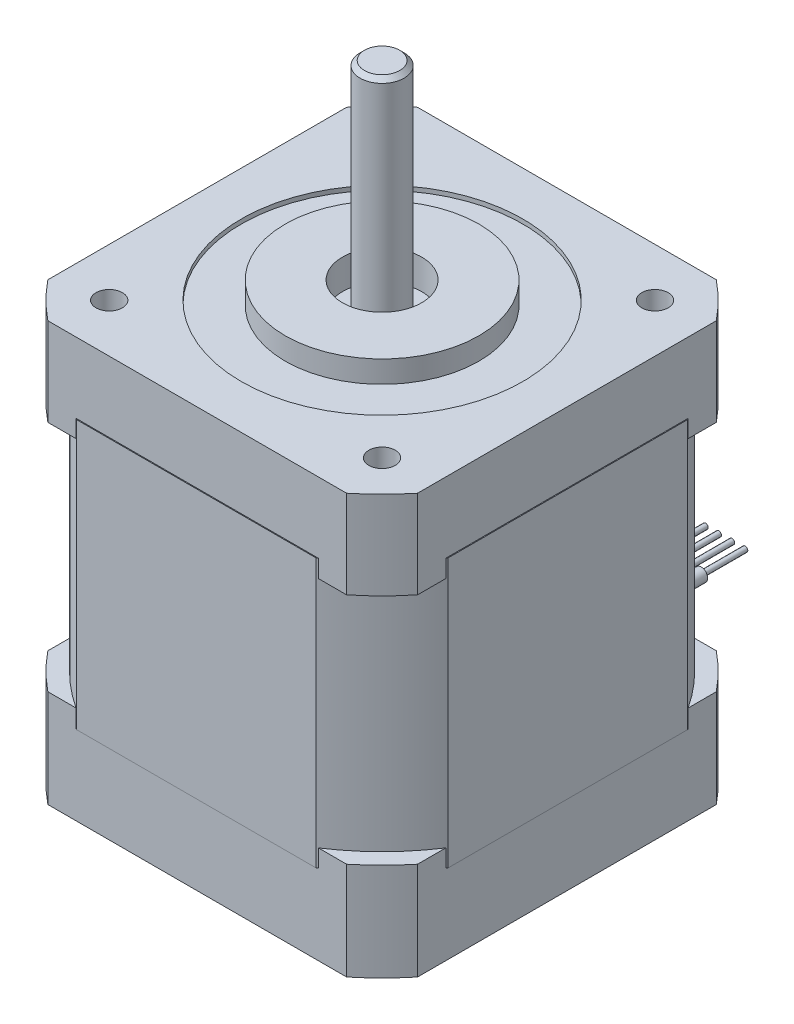
SolidWorks part; units mm, degrees
ref_plane "前视基准面" through (0, 0, 0) normal (0, 0, 1) x (1, 0, 0)
ref_plane "上视基准面" through (0, 0, 0) normal (0, 1, 0) x (1, 0, 0)
ref_plane "右视基准面" through (0, 0, 0) normal (1, 0, 0) x (0, 0, -1)
sketch "草图2" plane through (0, 0, 0) normal (0, 1, 0) x (1, 0, 0)
  line L1 (16.9706, 21) -> (-16.9706, 21)
  line L2 (21, 16.9706) -> (21, -16.9706)
  line L3 (16.9706, -21) -> (-16.9706, -21)
  line L4 (-21, 16.9706) -> (-21, -16.9706)
  arc A0 (-21, -16.9706) -> (-16.9706, -21) centre (0, 0) ccw
  arc A1 (-16.9706, 21) -> (-21, 16.9706) centre (0, 0) ccw
  arc A2 (21, 16.9706) -> (16.9706, 21) centre (0, 0) ccw
  arc A3 (16.9706, -21) -> (21, -16.9706) centre (0, 0) ccw
  circle A4 centre (-15.5, 15.5) radius 1.5
  circle A5 centre (15.5, 15.5) radius 1.5
  circle A6 centre (15.5, -15.5) radius 1.5
  circle A7 centre (-15.5, -15.5) radius 1.5
  point P0 (0, 0)
  dimension "D1" = 42
  dimension "D2" = 42
extrude "凸台-拉伸2" add sketch "草图2" along normal blind 8
sketch "草图3" plane through (0, 8, 0) normal (0, 1, 0) x (1, 0, 0)
  circle A0 centre (0, 0) radius 16
extrude "切除-拉伸1" cut sketch "草图3" against normal blind 0.5
sketch "草图4" plane through (0, 7.5, 0) normal (0, 1, 0) x (1, 0, 0)
  circle A0 centre (0, 0) radius 11
extrude "凸台-拉伸3" add sketch "草图4" along normal blind 2.5
sketch "草图5" plane through (0, 10, 0) normal (0, 1, 0) x (1, 0, 0)
  circle A0 centre (0, 0) radius 4.5
extrude "切除-拉伸2" cut sketch "草图5" against normal blind 3.4
sketch "草图6" plane through (0, 6.6, 0) normal (0, 1, 0) x (1, 0, 0)
  circle A0 centre (0, 0) radius 2.5
extrude "凸台-拉伸4" add sketch "草图6" along normal blind 25
chamfer "倒角2" distance 0.5 angle 45 1 edges at (0, 31.6, 2.5)
extrude "凸台-拉伸5" add sketch "草图2<2>" against normal blind 2
sketch "草图2<2>" plane through (0, 0, 0) normal (0, 1, 0) x (1, 0, 0) same geometry as "草图2"
sketch "草图7" plane through (0, 0, 0) normal (0, 1, 0) x (1, 0, 0)
  line L1 (13.6126, 21.1) -> (-13.6126, 21.1)
  line L2 (21.1, 13.6126) -> (21.1, -13.6126)
  line L3 (13.6126, -21.1) -> (-13.6126, -21.1)
  line L4 (-21.1, 13.6126) -> (-21.1, -13.6126)
  circle A0 centre (-15.5, 15.5) radius 1.5
  circle A1 centre (15.5, 15.5) radius 1.5
  circle A2 centre (-15.5, -15.5) radius 1.5
  circle A3 centre (15.5, -15.5) radius 1.5
  arc A4 (-21.1, -13.6126) -> (-13.6126, -21.1) centre (0, 0) ccw
  arc A5 (13.6126, -21.1) -> (21.1, -13.6126) centre (0, 0) ccw
  arc A6 (21.1, 13.6126) -> (13.6126, 21.1) centre (0, 0) ccw
  arc A7 (-13.6126, 21.1) -> (-21.1, 13.6126) centre (0, 0) ccw
  point P0 (0, 0)
extrude "凸台-拉伸6" add sketch "草图7" against normal blind 30.5
sketch "草图8" plane through (0, -30.5, 0) normal (0, -1, 0) x (1, 0, 0)
  line L0 (16.9706, 21) -> (-16.9706, 21)
  line L1 (21, 16.9706) -> (21, -16.9706)
  line L2 (16.9706, -21) -> (-16.9706, -21)
  line L3 (-21, 16.9706) -> (-21, -16.9706)
  arc A0 (-21, -16.9706) -> (-16.9706, -21) centre (0, 0) ccw
  arc A1 (-16.9706, 21) -> (-21, 16.9706) centre (0, 0) ccw
  arc A2 (21, 16.9706) -> (16.9706, 21) centre (0, 0) ccw
  arc A3 (16.9706, -21) -> (21, -16.9706) centre (0, 0) ccw
  circle A4 centre (-15.5, 15.5) radius 1.5
  circle A5 centre (15.5, 15.5) radius 1.5
  circle A6 centre (15.5, -15.5) radius 1.5
  circle A7 centre (-15.5, -15.5) radius 1.5
  point P0 (0, 0)
extrude "凸台-拉伸8" add sketch "草图8" against normal blind 2
extrude "凸台-拉伸9" add sketch "草图8<3>" along normal blind 9.1
sketch "草图8<3>" plane through (0, -30.5, 0) normal (0, -1, 0) x (1, 0, 0) same geometry as "草图8"
sketch "草图9" plane through (0, -39.6, 0) normal (0, -1, 0) x (1, 0, 0)
  circle A0 centre (0, 0) radius 3.5
  circle A1 centre (-15.5, 15.5) radius 3
  circle A2 centre (15.5, 15.5) radius 3
  circle A3 centre (-15.5, -15.5) radius 3
  circle A4 centre (15.5, -15.5) radius 3
extrude "切除-拉伸3" cut sketch "草图9" against normal blind 3.5
sketch "草图10" plane through (0, -36.1, 0) normal (0, -1, 0) x (1, 0, 0)
  circle A0 centre (15.5, -15.5) radius 2.5
  circle A1 centre (15.5, 15.5) radius 2.5
  circle A2 centre (-15.5, 15.5) radius 2.5
  circle A3 centre (-15.5, -15.5) radius 2.5
extrude "凸台-拉伸10" add sketch "草图10" along normal blind 3
extrude "凸台-拉伸11" add sketch "草图10<2>" against normal blind 39
sketch "草图10<2>" plane through (0, -36.1, 0) normal (0, -1, 0) x (1, 0, 0) same geometry as "草图10"
fillet "圆角2" radius 2 1 edges at (-15.5, -39.1, -18) type face fillet first side face at (-15.5, -39.1, -18) second side face at (-15.5, -39.1, -18)
fillet "圆角3" radius 2 1 edges at (15.5, -39.1, -18) type face fillet first side face at (15.5, -39.1, -18) second side face at (15.5, -39.1, -18)
fillet "圆角4" radius 2 1 edges at (15.5, -39.1, 13) type face fillet first side face at (15.5, -39.1, 13) second side face at (15.5, -39.1, 13)
fillet "圆角5" radius 2 1 edges at (-15.5, -39.1, 13) type face fillet first side face at (-15.5, -39.1, 13) second side face at (-15.5, -39.1, 13)
sketch "草图11" plane through (0, -39.6, 0) normal (0, -1, 0) x (1, 0, 0)
  line L1 (-15.5, 17.1) -> (-15.2, 17.1)
  line L2 (-15.2, 17.1) -> (-15.2, 15.8)
  line L3 (-15.2, 15.8) -> (-13.9, 15.8)
  line L4 (-13.9, 15.8) -> (-13.9, 15.2)
  line L5 (-13.9, 15.2) -> (-15.2, 15.2)
  line L6 (-15.2, 15.2) -> (-15.2, 13.9)
  line L7 (-15.2, 13.9) -> (-15.8, 13.9)
  line L8 (-15.8, 13.9) -> (-15.8, 15.2)
  line L9 (-15.8, 15.2) -> (-17.1, 15.2)
  line L10 (-17.1, 15.2) -> (-17.1, 15.8)
  line L11 (-17.1, 15.8) -> (-15.8, 15.8)
  line L12 (-15.8, 15.8) -> (-15.8, 17.1)
  line L13 (-15.8, 17.1) -> (-15.5, 17.1)
  line L16 (15.8, 17.1) -> (15.5, 17.1)
  line L17 (15.8, 15.8) -> (15.8, 17.1)
  line L18 (17.1, 15.8) -> (15.8, 15.8)
  line L19 (17.1, 15.2) -> (17.1, 15.8)
  line L20 (15.8, 15.2) -> (17.1, 15.2)
  line L21 (15.8, 13.9) -> (15.8, 15.2)
  line L22 (15.2, 13.9) -> (15.8, 13.9)
  line L23 (15.2, 15.2) -> (15.2, 13.9)
  line L24 (13.9, 15.2) -> (15.2, 15.2)
  line L25 (13.9, 15.8) -> (13.9, 15.2)
  line L26 (15.2, 15.8) -> (13.9, 15.8)
  line L27 (15.2, 17.1) -> (15.2, 15.8)
  line L28 (15.5, 17.1) -> (15.2, 17.1)
  line L30 (15.5, -17.1) -> (15.2, -17.1)
  line L31 (15.2, -17.1) -> (15.2, -15.8)
  line L32 (15.2, -15.8) -> (13.9, -15.8)
  line L33 (13.9, -15.8) -> (13.9, -15.2)
  line L34 (13.9, -15.2) -> (15.2, -15.2)
  line L35 (15.2, -15.2) -> (15.2, -13.9)
  line L36 (15.2, -13.9) -> (15.8, -13.9)
  line L37 (15.8, -13.9) -> (15.8, -15.2)
  line L38 (15.8, -15.2) -> (17.1, -15.2)
  line L39 (17.1, -15.2) -> (17.1, -15.8)
  line L40 (17.1, -15.8) -> (15.8, -15.8)
  line L41 (15.8, -15.8) -> (15.8, -17.1)
  line L42 (15.8, -17.1) -> (15.5, -17.1)
  line L43 (-15.8, -17.1) -> (-15.5, -17.1)
  line L44 (-15.8, -15.8) -> (-15.8, -17.1)
  line L45 (-17.1, -15.8) -> (-15.8, -15.8)
  line L46 (-17.1, -15.2) -> (-17.1, -15.8)
  line L47 (-15.8, -15.2) -> (-17.1, -15.2)
  line L48 (-15.8, -13.9) -> (-15.8, -15.2)
  line L49 (-15.2, -13.9) -> (-15.8, -13.9)
  line L50 (-15.2, -15.2) -> (-15.2, -13.9)
  line L51 (-13.9, -15.2) -> (-15.2, -15.2)
  line L52 (-13.9, -15.8) -> (-13.9, -15.2)
  line L53 (-15.2, -15.8) -> (-13.9, -15.8)
  line L54 (-15.2, -17.1) -> (-15.2, -15.8)
  line L55 (-15.5, -17.1) -> (-15.2, -17.1)
extrude "切除-拉伸4" cut sketch "草图11" against normal blind 3.5
sketch "草图12" plane through (0, 0, -21) normal (0, 0, -1) x (-1, 0, 0)
  line L2 (0, -35.6) -> (3, -35.6)
  line L3 (3, -35.6) -> (3, -34.1)
  line L4 (3, -34.1) -> (-3, -34.1)
  line L5 (-3, -34.1) -> (-3, -35.6)
  line L6 (-3, -35.6) -> (0, -35.6)
extrude "切除-拉伸5" cut sketch "草图12" against normal blind 2
sketch "草图13" plane through (0, 0, -19) normal (0, 0, -1) x (-1, 0, 0)
  circle A0 centre (-0.75, -34.85) radius 0.74
  circle A1 centre (-2.25, -34.85) radius 0.74
  circle A2 centre (0.75, -34.85) radius 0.74
  circle A3 centre (2.25, -34.85) radius 0.74
extrude "凸台-拉伸16" add sketch "草图13" along normal blind 15
sketch "草图14" plane through (0, 0, -34) normal (0, 0, -1) x (-1, 0, 0)
  circle A0 centre (-2.25, -34.85) radius 0.3
  circle A1 centre (-0.75, -34.85) radius 0.3
  circle A2 centre (0.75, -34.85) radius 0.3
  circle A3 centre (2.25, -34.85) radius 0.3
extrude "凸台-拉伸17" add sketch "草图14" along normal blind 5
